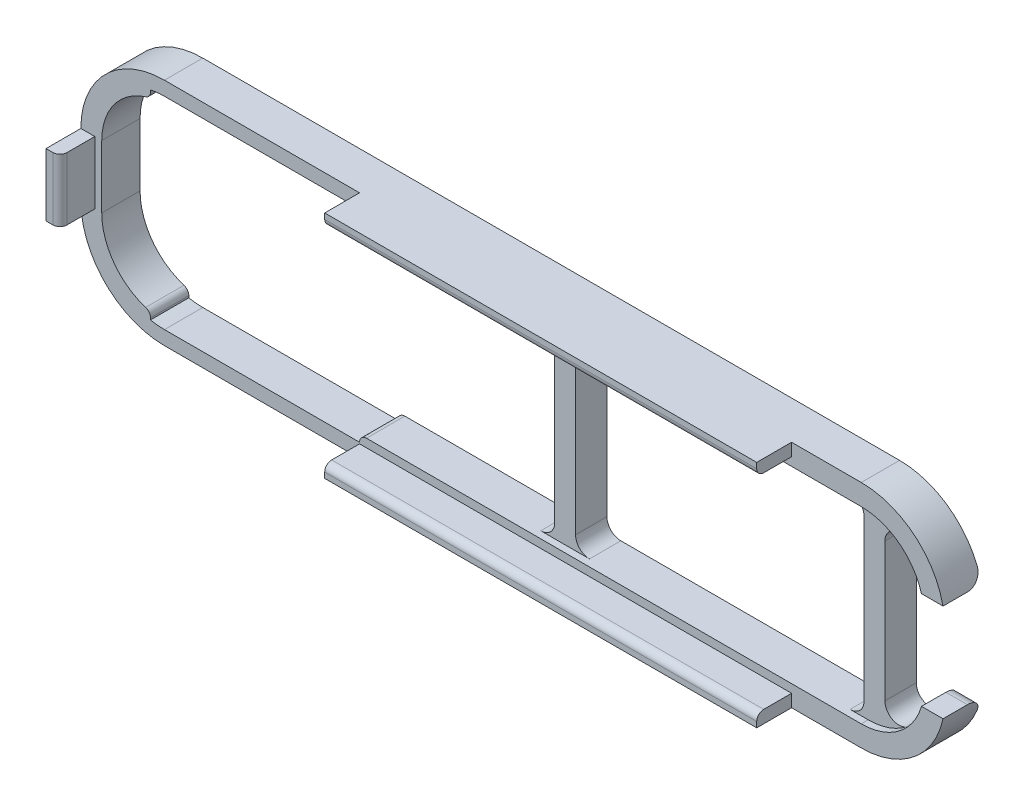
SolidWorks part; units mm, degrees
ref_plane "Front" through (0, 0, 0) normal (0, 0, 1) x (1, 0, 0)
ref_plane "Top" through (0, 0, 0) normal (0, 1, 0) x (1, 0, 0)
ref_plane "Right" through (0, 0, 0) normal (1, 0, 0) x (0, 0, -1)
sketch "Sketch1 - footprint" plane through (0, 0, 0) normal (0, 0, 1) x (1, 0, 0)
  line L1 (10, 14.5) -> (110, 14.5) construction
  line L2 (0, 4.5) -> (0, -4.5) construction
  line L3 (10, -14.5) -> (110, -14.5) construction
  line L4 (120, 4.5) -> (120, -4.5) construction
  arc A0 (110, 14.5) -> (120, 4.5) centre (110, 4.5) cw construction
  arc A1 (120, -4.5) -> (110, -14.5) centre (110, -4.5) cw construction
  arc A2 (10, -14.5) -> (0, -4.5) centre (10, -4.5) cw construction
  arc A3 (0, 4.5) -> (10, 14.5) centre (10, 4.5) cw construction
  point P4 (0, 0)
  point P8 (120, 14.5)
  point P13 (0, -14.5)
  point P16 (0, 14.5)
  dimension "D3" = 10
  dimension "D1" = 120
  dimension "D2" = 29
sketch "Sketch2" plane through (0, 0, 0) normal (0, 0, 1) x (1, 0, 0)
  line L4 (122.25, -4.5) -> (122.25, 4.5)
  line L5 (110, 16.75) -> (10, 16.75)
  line L6 (-2.25, 4.5) -> (-2.25, -4.5)
  line L7 (10, -16.75) -> (110, -16.75)
  line L8 (120.25, -4.5) -> (120.25, 4.5)
  line L9 (10, -14.75) -> (110, -14.75)
  line L10 (-0.25, 4.5) -> (-0.25, -4.5)
  line L11 (110, 14.75) -> (10, 14.75)
  line L12 (120.25, -4.5) -> (120.25, 4.5)
  line L13 (10, -14.75) -> (110, -14.75)
  line L14 (-0.25, 4.5) -> (-0.25, -4.5)
  line L15 (110, 14.75) -> (10, 14.75)
  arc A4 (122.25, 4.5) -> (110, 16.75) centre (110, 4.5) ccw
  arc A5 (10, 16.75) -> (-2.25, 4.5) centre (10, 4.5) ccw
  arc A6 (-2.25, -4.5) -> (10, -16.75) centre (10, -4.5) ccw
  arc A7 (110, -16.75) -> (122.25, -4.5) centre (110, -4.5) ccw
  arc A8 (120.25, 4.5) -> (110, 14.75) centre (110, 4.5) ccw
  arc A9 (110, -14.75) -> (120.25, -4.5) centre (110, -4.5) ccw
  arc A10 (-0.25, -4.5) -> (10, -14.75) centre (10, -4.5) ccw
  arc A11 (10, 14.75) -> (-0.25, 4.5) centre (10, 4.5) ccw
  arc A12 (120.25, 4.5) -> (110, 14.75) centre (110, 4.5) ccw
  arc A13 (110, -14.75) -> (120.25, -4.5) centre (110, -4.5) ccw
  arc A14 (-0.25, -4.5) -> (10, -14.75) centre (10, -4.5) ccw
  arc A15 (10, 14.75) -> (-0.25, 4.5) centre (10, 4.5) ccw
  dimension "D1" = 0.25
  dimension "D2" = 2
ref_plane "Plane1 - PCB bottom plane" through (0, 0, -1.6194) normal (0, 0, 1) x (1, 0, 0)
sketch "Sketch3" plane through (0, 0, -1.6194) normal (0, 0, 1) x (1, 0, 0)
  line L9 (119, -4.5) -> (119, 4.5)
  line L10 (10, -13.5) -> (110, -13.5)
  line L11 (1, 4.5) -> (1, -4.5)
  line L12 (110, 13.5) -> (10, 13.5)
  line L13 (119, -4.5) -> (119, 4.5)
  line L14 (10, -13.5) -> (110, -13.5)
  line L15 (1, 4.5) -> (1, -4.5)
  line L16 (110, 13.5) -> (10, 13.5)
  line L24 (110, 16.5) -> (10, 16.5)
  line L25 (122, -4.5) -> (122, 4.5)
  line L26 (10, -16.5) -> (110, -16.5)
  line L27 (-2, 4.5) -> (-2, -4.5)
  line L28 (110, 16.5) -> (10, 16.5)
  line L29 (122, -4.5) -> (122, 4.5)
  line L30 (10, -16.5) -> (110, -16.5)
  line L31 (-2, 4.5) -> (-2, -4.5)
  arc A8 (119, 4.5) -> (110, 13.5) centre (110, 4.5) ccw
  arc A9 (110, -13.5) -> (119, -4.5) centre (110, -4.5) ccw
  arc A10 (1, -4.5) -> (10, -13.5) centre (10, -4.5) ccw
  arc A11 (10, 13.5) -> (1, 4.5) centre (10, 4.5) ccw
  arc A12 (119, 4.5) -> (110, 13.5) centre (110, 4.5) ccw
  arc A13 (110, -13.5) -> (119, -4.5) centre (110, -4.5) ccw
  arc A14 (1, -4.5) -> (10, -13.5) centre (10, -4.5) ccw
  arc A15 (10, 13.5) -> (1, 4.5) centre (10, 4.5) ccw
  arc A23 (122, 4.5) -> (110, 16.5) centre (110, 4.5) ccw
  arc A24 (110, -16.5) -> (122, -4.5) centre (110, -4.5) ccw
  arc A25 (-2, -4.5) -> (10, -16.5) centre (10, -4.5) ccw
  arc A26 (10, 16.5) -> (-2, 4.5) centre (10, 4.5) ccw
  arc A27 (122, 4.5) -> (110, 16.5) centre (110, 4.5) ccw
  arc A28 (110, -16.5) -> (122, -4.5) centre (110, -4.5) ccw
  arc A29 (-2, -4.5) -> (10, -16.5) centre (10, -4.5) ccw
  arc A30 (10, 16.5) -> (-2, 4.5) centre (10, 4.5) ccw
  dimension "D1" = 1
  dimension "D2" = 2
extrude "Boss-Extrude2" add sketch "Sketch3" against normal blind 5.5
sketch "Sketch4" plane through (0, 0, -1.6194) normal (0, 0, 1) x (1, 0, 0)
  line L6 (88, -13.5) -> (88, 13.5) construction
  line L7 (10, -13.5) -> (110, -13.5) construction
  line L9 (110, 13.5) -> (10, 13.5) construction
  line L10 (120, 4.5) -> (120, -4.5) construction
  line L11 (10, -13.5) -> (110, -13.5) construction
  line L12 (109.4, -13.5) -> (112.4, -13.5)
  line L13 (109.4, -13.5) -> (109.4, 13.5)
  line L14 (109.4, 13.5) -> (112.4, 13.5)
  line L15 (112.4, -13.5) -> (112.4, 13.5)
  line L17 (65, -13.5) -> (68, -13.5)
  line L18 (65, -13.5) -> (65, 13.5)
  line L19 (65, 13.5) -> (68, 13.5)
  line L20 (68, -13.5) -> (68, 13.5)
  point P16 (120, 0)
  dimension "D1" = 32
  dimension "D2" = 3
  dimension "D3" = 7.6
  dimension "D4" = 3
  dimension "D5" = 52
  dimension "D6" = 20
extrude "Boss-Extrude4 - cross structures" add sketch "Sketch4" against normal up to surface (5.5 mm away) up to face at (60, 0, -7.1194)
sketch "Sketch6" plane through (0, 0, -1.6194) normal (0, 0, 1) x (1, 0, 0)
  line L0 (109.4, 13.5) -> (110, 13.5)
  line L1 (112.4, 13.1741) -> (112.4, -13.1741)
  line L2 (109.4, -13.5) -> (110, -13.5)
  line L4 (109.4, -13.5) -> (112.4, -13.5)
  line L5 (112.4, -13.5) -> (112.4, 13.5)
  line L6 (112.4, 13.5) -> (109.4, 13.5)
  line L7 (109.4, 13.5) -> (109.4, -13.5)
  line L11 (109.4, 13.5) -> (109.4, -13.5)
  line L12 (65, -13.5) -> (68, -13.5)
  line L13 (68, -13.5) -> (68, 13.5)
  line L14 (68, 13.5) -> (65, 13.5)
  line L15 (65, 13.5) -> (65, -13.5)
  line L16 (65, -13.5) -> (68, -13.5)
  line L17 (68, -13.5) -> (68, 13.5)
  line L18 (68, 13.5) -> (65, 13.5)
  line L19 (65, 13.5) -> (65, -13.5)
  arc A0 (110, 13.5) -> (112.4, 13.1741) centre (110, 4.5) cw
  arc A1 (119, 4.5) -> (112.4, 13.1741) centre (110, 4.5) ccw construction
  arc A2 (110, -13.5) -> (112.4, -13.1741) centre (110, -4.5) ccw
  arc A3 (112.4, -13.1741) -> (119, -4.5) centre (110, -4.5) ccw construction
  dimension "D1" = 0
  dimension "D2" = 0
extrude "Cut-Extrude3 - 1 mm spacing" cut sketch "Sketch6" against normal blind 1
sketch "Sketch7" plane through (0, 0, -1.6194) normal (0, 0, 1) x (1, 0, 0)
  line L0 (10, -14.5) -> (110, -14.5) construction
  line L1 (38, -14.5) -> (10, -14.5)
  line L2 (38, -14.5) -> (38, 14.5)
  line L3 (38, 14.5) -> (10, 14.5)
  line L5 (10, 14.5) -> (110, 14.5) construction
  line L6 (0, 4.5) -> (0, -4.5) construction
  line L7 (8, 14.298) -> (8, -14.298)
  arc A0 (10, 14.5) -> (0, 4.5) centre (10, 4.5) ccw construction
  arc A1 (0, -4.5) -> (10, -14.5) centre (10, -4.5) ccw construction
  arc A2 (10, -14.5) -> (8, -14.298) centre (10, -4.5) cw
  arc A3 (10, 14.5) -> (8, 14.298) centre (10, 4.5) ccw
  dimension "D1" = 38
  dimension "D2" = 30
extrude "Cut-Extrude4 - electronics spacing" cut sketch "Sketch7" against normal through all
sketch "Sketch8" plane through (122, 0, 0) normal (1, 0, 0) x (0, 0, -1)
  line L0 (1.6194, -7) -> (7.1194, -7)
  line L1 (1.6194, -4.5) -> (1.6194, -16.5) construction
  line L2 (7.1194, -7) -> (7.1194, 7)
  line L3 (7.1194, 7) -> (1.6194, 7)
  line L4 (1.6194, 16.5) -> (1.6194, 4.5) construction
  line L5 (1.6194, -7) -> (1.6194, 7)
  line L6 (7.1194, -4.5) -> (7.1194, 4.5) construction
  point P8 (1.6194, 0)
  dimension "D1" = 14
extrude "Cut-Extrude2 - USB-C cutout" cut sketch "Sketch8" against normal blind 5
sketch "Sketch10" plane through (0, 0, -1.6194) normal (0, 0, 1) x (1, 0, 0)
  line L1 (1, 1.2) -> (3, 1.2)
  line L2 (1, 1.2) -> (1, -1.2)
  line L3 (1, -1.2) -> (3, -1.2)
  line L4 (3, 1.2) -> (3, -1.2)
  line L5 (1, 4.5) -> (1, -4.5) construction
  point P6 (1, 0)
  dimension "D1" = 2.4
  dimension "D2" = 2
extrude "Boss-Extrude3" [suppressed] add sketch "Sketch10" against normal up to surface (5.5 mm away) contours L4 L3 L2 L1
sketch "Sketch11" [suppressed] plane through (0, 0, 0) normal (0, 1, 0) x (1, 0, 0)
  line L0 (3, 2.2194) -> (-2, 4.6194)
  line L1 (3, 7.1194) -> (3, 1.6194) construction
  line L2 (-2, 7.1194) -> (-2, 1.6194) construction
  line L3 (-2, 4.6194) -> (-2, 1.6194)
  line L4 (-2, 1.6194) -> (3, 1.6194)
  line L5 (3, 1.6194) -> (3, 2.2194)
  dimension "D1" = 0.6
  dimension "D2" = 3
extrude "Cut-Extrude1 - LED opening" [suppressed] cut sketch "Sketch11" against normal mid plane 2.4
fillet "Fillet4 - LED light" [suppressed] radius 1
sketch "Sketch12" plane through (0, 0, -7.1194) normal (0, 0, -1) x (-1, 0, 0)
  line L0 (-10, -16.5) -> (-110, -16.5) construction
  line L1 (-41, -16.5) -> (-51, -16.5)
  line L2 (-41, -16.5) -> (-41, -18.5)
  line L3 (-41, -18.5) -> (-51, -18.5)
  line L4 (-51, -16.5) -> (-51, -18.5)
  line L6 (-97, -16.5) -> (-107, -16.5)
  line L7 (-97, -16.5) -> (-97, -18.5)
  line L8 (-97, -18.5) -> (-107, -18.5)
  line L9 (-107, -16.5) -> (-107, -18.5)
  point P10 (-46, -16.5)
  point P12 (-102, -16.5)
  dimension "D1" = 46
  dimension "D2" = 102
  dimension "D3" = 10
  dimension "D4" = 2
extrude "Boss-Extrude4 - snap bumps" [suppressed] add sketch "Sketch12" against normal up to surface (5.5 mm away)
sketch "Sketch13" [suppressed] plane through (0, 0, -7.1194) normal (0, 0, -1) x (-1, 0, 0)
  line L0 (-51, -18.5) -> (-41, -18.5) construction
  line L1 (-43.5, -18.5) -> (-48.5, -18.5)
  line L2 (-43.5, -18.5) -> (-43.5, -14.5)
  line L3 (-43.5, -14.5) -> (-48.5, -14.5)
  line L4 (-48.5, -18.5) -> (-48.5, -14.5)
  line L6 (-107, -18.5) -> (-97, -18.5) construction
  line L7 (-99.5, -18.5) -> (-104.5, -18.5)
  line L8 (-99.5, -18.5) -> (-99.5, -14.5)
  line L9 (-99.5, -14.5) -> (-104.5, -14.5)
  line L10 (-104.5, -18.5) -> (-104.5, -14.5)
  point P8 (-46, -18.5)
  point P9 (-46, -18.5)
  point P14 (-102, -18.5)
  point P15 (-102, -18.5)
  dimension "D1" = 5
  dimension "D2" = 4
extrude "Cut-Extrude2 - snap seat (2.15, original is 2.0)" [suppressed] cut sketch "Sketch13" against normal blind 2.15
sketch "Sketch14" [suppressed] plane through (0, 0, -4.9694) normal (0, 0, -1) x (-1, 0, 0)
  line L0 (-48.5, -14.5) -> (-48.5, -18.5) construction
  line L1 (-43.5, -14.5) -> (-48.5, -14.5)
  line L2 (-43.5, -14.5) -> (-43.5, -17.35)
  line L3 (-43.5, -17.35) -> (-48.5, -17.35)
  line L4 (-48.5, -14.5) -> (-48.5, -17.35)
  line L6 (-51, -16.5) -> (-97, -16.5) construction
  line L7 (-99.5, -14.5) -> (-104.5, -14.5)
  line L8 (-99.5, -14.5) -> (-99.5, -17.35)
  line L9 (-99.5, -17.35) -> (-104.5, -17.35)
  line L10 (-104.5, -14.5) -> (-104.5, -17.35)
  line L13 (-99.5, -18.5) -> (-99.5, -14.5) construction
  dimension "D1" = 0.85
extrude "Cut-Extrude3 - snap post cut" [suppressed] cut sketch "Sketch14" against normal through all
sketch "Sketch15" [suppressed] plane through (0, 0, -7.1194) normal (0, 0, -1) x (-1, 0, 0)
  line L0 (-38, -13.5) -> (-65, -13.5) construction
  line L1 (-41, -13.5) -> (-51, -13.5)
  line L2 (-41, -13.5) -> (-41, -12.5)
  line L3 (-41, -12.5) -> (-51, -12.5)
  line L4 (-51, -13.5) -> (-51, -12.5)
  line L5 (-68, -13.5) -> (-109.4, -13.5) construction
  line L6 (-97, -13.5) -> (-107, -13.5)
  line L7 (-97, -13.5) -> (-97, -12.5)
  line L8 (-97, -12.5) -> (-107, -12.5)
  line L9 (-107, -13.5) -> (-107, -12.5)
  line L10 (-41, -18.5) -> (-41, -16.5) construction
  line L11 (-51, -16.5) -> (-51, -18.5) construction
  line L12 (-97, -18.5) -> (-97, -16.5) construction
  line L13 (-107, -16.5) -> (-107, -18.5) construction
  dimension "D1" = 1
extrude "Boss-Extrude4" [suppressed] add sketch "Sketch15" against normal up to surface (4.5 mm away)
mirror "Mirror1" [suppressed] about plane through (0, 0, 0) normal (0, 1, 0)
fillet "Fillet6 - snap features" [suppressed] radius 1
fillet "Fillet2 - USBC" radius 2 2 edges at (120.1913, 7, -7.1194) (120.1913, -7, -7.1194)
fillet "Fillet3 - inner corners, front" radius 1 4 edges at (38, 13.5, -4.3694) (38, -13.5, -4.3694) (8, -13.275, -4.3694) (8, 13.275, -4.3694)
fillet "Fillet5 - inner corners" radius 2 8 edges at (112.4, -13.1741, -4.8694) (112.4, 13.1741, -4.8694) (109.4, 13.5, -4.8694) (109.4, -13.5, -4.8694) (68, -13.5, -4.8694) (68, 13.5, -4.8694) (65, 13.5, -4.8694) (65, -13.5, -4.8694)
sketch "Sketch16" [suppressed] plane through (0, 0, -7.1194) normal (0, 0, -1) x (-1, 0, 0)
  line L0 (-98, -12.5) -> (-106, -12.5) construction
  line L1 (-109.4, -11.5) -> (-109.4, 11.5) construction
  line L2 (-98, 12.5) -> (-106, 12.5) construction
  line L3 (-97, 13.5) -> (-70, 13.5) construction
  line L4 (-70, -13.5) -> (-97, -13.5) construction
  line L5 (-68, 11.5) -> (-68, -11.5) construction
  line L6 (-38, 14.5) -> (-10, 14.5) construction
  line L7 (-41, 13.5) -> (-39, 13.5) construction
  line L8 (-42, 12.5) -> (-50, 12.5) construction
  line L9 (-63, 13.5) -> (-51, 13.5) construction
  line L10 (-65, -11.5) -> (-65, 11.5) construction
  line L11 (-51, -13.5) -> (-63, -13.5) construction
  line L12 (-42, -12.5) -> (-50, -12.5) construction
  line L13 (-39, -13.5) -> (-41, -13.5) construction
  line L14 (-10, -14.5) -> (-38, -14.5) construction
  line L15 (-98, -12.5) -> (-106, -12.5)
  line L16 (-109.4, -11.5) -> (-109.4, 11.5)
  line L17 (-98, 12.5) -> (-106, 12.5)
  line L18 (-97, 13.5) -> (-70, 13.5)
  line L19 (-70, -13.5) -> (-97, -13.5)
  line L20 (-68, 11.5) -> (-68, -11.5)
  line L21 (-38, 14.5) -> (-10, 14.5)
  line L22 (-41, 13.5) -> (-39, 13.5)
  line L23 (-42, 12.5) -> (-50, 12.5)
  line L24 (-63, 13.5) -> (-51, 13.5)
  line L25 (-65, -11.5) -> (-65, 11.5)
  line L26 (-51, -13.5) -> (-63, -13.5)
  line L27 (-42, -12.5) -> (-50, -12.5)
  line L28 (-39, -13.5) -> (-41, -13.5)
  line L29 (-10, -14.5) -> (-38, -14.5)
  line L30 (-1, -2.2) -> (-1, -4.5) construction
  line L31 (-1, -2.2) -> (-1, -4.5)
  line L32 (-1, 4.5) -> (-1, 2.2) construction
  line L33 (-1, 4.5) -> (-1, 2.2)
  line L34 (-107, -13.5) -> (-107.4, -13.5) construction
  line L35 (-107, -13.5) -> (-107.4, -13.5)
  line L36 (-107.4, 13.5) -> (-107, 13.5) construction
  line L37 (-107.4, 13.5) -> (-107, 13.5)
  line L38 (-3, -0.2) -> (-3, 0.2) construction
  line L39 (-3, -0.2) -> (-3, 0.2)
  line L40 (-8, -14.0394) -> (-8, -14.298) construction
  line L41 (-8, -14.0394) -> (-8, -14.298)
  line L42 (-8, 14.298) -> (-8, 14.0394) construction
  line L43 (-8, 14.298) -> (-8, 14.0394)
  arc A0 (-97, -13.5) -> (-98, -12.5) centre (-98, -13.5) ccw construction
  arc A1 (-106, -12.5) -> (-107, -13.5) centre (-106, -13.5) ccw construction
  arc A2 (-109.4, -11.5) -> (-107.4, -13.5) centre (-107.4, -11.5) ccw construction
  arc A3 (-107.4, 13.5) -> (-109.4, 11.5) centre (-107.4, 11.5) ccw construction
  arc A4 (-107, 13.5) -> (-106, 12.5) centre (-106, 13.5) ccw construction
  arc A5 (-98, 12.5) -> (-97, 13.5) centre (-98, 13.5) ccw construction
  arc A6 (-70, -13.5) -> (-68, -11.5) centre (-70, -11.5) ccw construction
  arc A7 (-68, 11.5) -> (-70, 13.5) centre (-70, 11.5) ccw construction
  arc A8 (-1, -2.2) -> (-2, -1.2) centre (-2, -2.2) ccw construction
  arc A9 (-3, -0.2) -> (-2, -1.2) centre (-2, -0.2) ccw construction
  arc A10 (-2, 1.2) -> (-3, 0.2) centre (-2, 0.2) ccw construction
  arc A11 (-2, 1.2) -> (-1, 2.2) centre (-2, 2.2) ccw construction
  arc A12 (-1, 4.5) -> (-7.3, 13.0855) centre (-10, 4.5) ccw construction
  arc A13 (-8, 14.0394) -> (-7.3, 13.0855) centre (-7, 14.0394) ccw construction
  arc A14 (-8, 14.298) -> (-10, 14.5) centre (-10, 4.5) ccw construction
  arc A15 (-39, 13.5) -> (-38, 14.5) centre (-39, 14.5) ccw construction
  arc A16 (-42, 12.5) -> (-41, 13.5) centre (-42, 13.5) ccw construction
  arc A17 (-51, 13.5) -> (-50, 12.5) centre (-50, 13.5) ccw construction
  arc A18 (-63, 13.5) -> (-65, 11.5) centre (-63, 11.5) ccw construction
  arc A19 (-65, -11.5) -> (-63, -13.5) centre (-63, -11.5) ccw construction
  arc A20 (-50, -12.5) -> (-51, -13.5) centre (-50, -13.5) ccw construction
  arc A21 (-41, -13.5) -> (-42, -12.5) centre (-42, -13.5) ccw construction
  arc A22 (-38, -14.5) -> (-39, -13.5) centre (-39, -14.5) ccw construction
  arc A23 (-10, -14.5) -> (-8, -14.298) centre (-10, -4.5) ccw construction
  arc A24 (-7.3, -13.0855) -> (-8, -14.0394) centre (-7, -14.0394) ccw construction
  arc A25 (-7.3, -13.0855) -> (-1, -4.5) centre (-10, -4.5) ccw construction
  arc A26 (-97, -13.5) -> (-98, -12.5) centre (-98, -13.5) ccw
  arc A27 (-106, -12.5) -> (-107, -13.5) centre (-106, -13.5) ccw
  arc A28 (-109.4, -11.5) -> (-107.4, -13.5) centre (-107.4, -11.5) ccw
  arc A29 (-107.4, 13.5) -> (-109.4, 11.5) centre (-107.4, 11.5) ccw
  arc A30 (-107, 13.5) -> (-106, 12.5) centre (-106, 13.5) ccw
  arc A31 (-98, 12.5) -> (-97, 13.5) centre (-98, 13.5) ccw
  arc A32 (-70, -13.5) -> (-68, -11.5) centre (-70, -11.5) ccw
  arc A33 (-68, 11.5) -> (-70, 13.5) centre (-70, 11.5) ccw
  arc A34 (-1, -2.2) -> (-2, -1.2) centre (-2, -2.2) ccw
  arc A35 (-3, -0.2) -> (-2, -1.2) centre (-2, -0.2) ccw
  arc A36 (-2, 1.2) -> (-3, 0.2) centre (-2, 0.2) ccw
  arc A37 (-2, 1.2) -> (-1, 2.2) centre (-2, 2.2) ccw
  arc A38 (-1, 4.5) -> (-7.3, 13.0855) centre (-10, 4.5) ccw
  arc A39 (-8, 14.0394) -> (-7.3, 13.0855) centre (-7, 14.0394) ccw
  arc A40 (-8, 14.298) -> (-10, 14.5) centre (-10, 4.5) ccw
  arc A41 (-39, 13.5) -> (-38, 14.5) centre (-39, 14.5) ccw
  arc A42 (-42, 12.5) -> (-41, 13.5) centre (-42, 13.5) ccw
  arc A43 (-51, 13.5) -> (-50, 12.5) centre (-50, 13.5) ccw
  arc A44 (-63, 13.5) -> (-65, 11.5) centre (-63, 11.5) ccw
  arc A45 (-65, -11.5) -> (-63, -13.5) centre (-63, -11.5) ccw
  arc A46 (-50, -12.5) -> (-51, -13.5) centre (-50, -13.5) ccw
  arc A47 (-41, -13.5) -> (-42, -12.5) centre (-42, -13.5) ccw
  arc A48 (-38, -14.5) -> (-39, -13.5) centre (-39, -14.5) ccw
  arc A49 (-10, -14.5) -> (-8, -14.298) centre (-10, -4.5) ccw
  arc A50 (-7.3, -13.0855) -> (-8, -14.0394) centre (-7, -14.0394) ccw
  arc A51 (-7.3, -13.0855) -> (-1, -4.5) centre (-10, -4.5) ccw
extrude "Boss-Extrude5" [suppressed] add sketch "Sketch16" against normal blind 1
sketch "Sketch17" plane through (0, 0, -7.1194) normal (0, 0, -1) x (-1, 0, 0)
  line L0 (-112.4, 9.9443) -> (-112.4, -9.9443) construction
  line L1 (-112.4, 9.9443) -> (-112.4, -9.9443)
  arc A0 (-117.7942, -9) -> (-115.6571, -11.4998) centre (-110, -4.5) ccw construction
  arc A1 (-115.6571, -11.4998) -> (-112.4, -9.9443) centre (-114.4, -9.9443) ccw construction
  arc A2 (-112.4, 9.9443) -> (-115.6571, 11.4998) centre (-114.4, 9.9443) ccw construction
  arc A3 (-115.6571, 11.4998) -> (-117.7942, 9) centre (-110, 4.5) ccw construction
  arc A4 (-117.7942, -9) -> (-115.6571, -11.4998) centre (-110, -4.5) ccw
  arc A5 (-115.6571, -11.4998) -> (-112.4, -9.9443) centre (-114.4, -9.9443) ccw
  arc A6 (-112.4, 9.9443) -> (-115.6571, 11.4998) centre (-114.4, 9.9443) ccw
  arc A7 (-115.6571, 11.4998) -> (-117.7942, 9) centre (-110, 4.5) ccw
  arc A8 (-118.6458, -7) -> (-117.7942, -9) centre (-110, -4.5) ccw construction
  arc A9 (-117.7942, 9) -> (-118.6458, 7) centre (-110, 4.5) ccw construction
  arc A10 (-118.6458, -7) -> (-117.7942, -9) centre (-110, -4.5) ccw
  arc A11 (-117.7942, 9) -> (-118.6458, 7) centre (-110, 4.5) ccw
  arc A12 (-118.6458, 7) -> (-118.6458, -7) centre (-94.4375, 0) ccw
extrude "Boss-Extrude6" [suppressed] add sketch "Sketch17" against normal blind 1
sketch "Sketch18" plane through (0, 0, -1.6194) normal (0, 0, 1) x (1, 0, 0)
  line L0 (110, 16.5) -> (10, 16.5) construction
  line L1 (38, 16.5) -> (100, 16.5)
  line L2 (38, 16.5) -> (38, 14.7)
  line L3 (38, 14.7) -> (100, 14.7)
  line L4 (100, 16.5) -> (100, 14.7)
  line L6 (10, 14.5) -> (110, 14.5) construction
  line L7 (0, 4.5) -> (0, -4.5) construction
  line L8 (10, -16.5) -> (110, -16.5) construction
  line L9 (38, -16.5) -> (100, -16.5)
  line L10 (38, -16.5) -> (38, -14.7)
  line L11 (38, -14.7) -> (100, -14.7)
  line L12 (100, -16.5) -> (100, -14.7)
  line L13 (-2, 4.5) -> (-2, -4.5) construction
  line L14 (-2, 4.5) -> (0, 4.5)
  line L15 (-2, 4.5) -> (-2, -4.5)
  line L16 (-2, -4.5) -> (0, -4.5)
  line L17 (0, 4.5) -> (0, -4.5)
  dimension "D1" = 0.2
  dimension "D2" = 62
  dimension "D3" = 38
extrude "Boss-Extrude7" add sketch "Sketch18" along normal blind 5
fillet "Fillet1" radius 1 3 edges at (69, -14.7, 3.3806) (69, 14.7, 3.3806) (0, 0, 3.3806)
